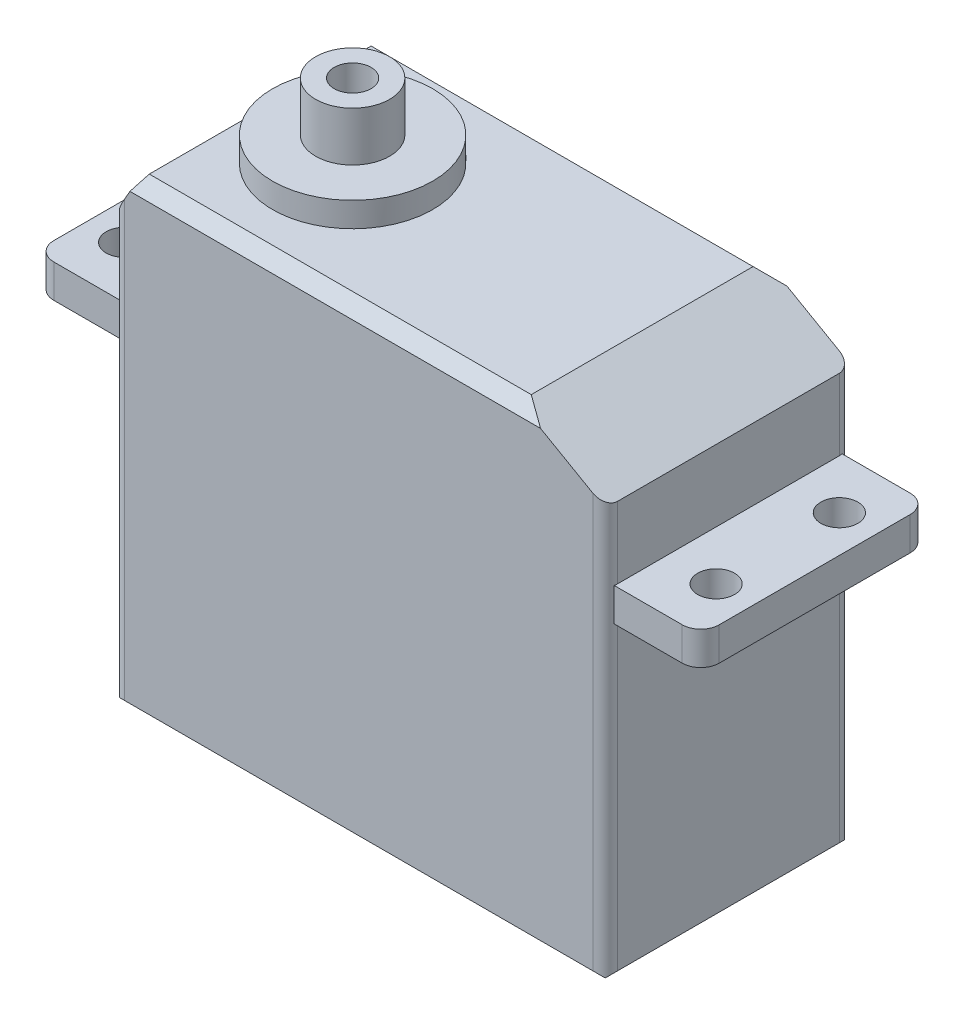
SolidWorks part; units mm, degrees
ref_plane "前视基准面" through (0, 0, 0) normal (0, 0, 1) x (1, 0, 0)
ref_plane "上视基准面" through (0, 0, 0) normal (0, 1, 0) x (1, 0, 0)
ref_plane "右视基准面" through (0, 0, 0) normal (1, 0, 0) x (0, 0, -1)
sketch "草图1" plane through (0, 0, 0) normal (0, 0, 1) x (1, 0, 0)
  line L1 (0, 0) -> (40, 0)
  line L2 (0, 0) -> (0, 39)
  line L3 (0, 39) -> (40, 39)
  line L4 (40, 0) -> (40, 39)
  dimension "D1" = 40
  dimension "D2" = 39
extrude "凸台-拉伸1" add sketch "草图1" along normal blind 20
sketch "草图2" plane through (0, 0, 0) normal (-1, 0, 0) x (0, 0, 1)
  line L0 (20, 0) -> (0, 0) construction
  line L1 (0.75, 29.2) -> (19.25, 29.2)
  line L2 (0.75, 29.2) -> (0.75, 26.5)
  line L3 (0.75, 26.5) -> (19.25, 26.5)
  line L4 (19.25, 29.2) -> (19.25, 26.5)
  line L5 (20, 39) -> (0, 39) construction
  point P8 (10, 39)
  point P9 (10, 29.2)
  dimension "D1" = 18.5
  dimension "D2" = 26.5
  dimension "D3" = 2.7
extrude "凸台-拉伸2" add sketch "草图2" along normal blind 7
sketch "草图3" plane through (40, 0, 0) normal (1, 0, 0) x (0, 0, -1)
  line L4 (-0.75, 26.5) -> (-0.75, 29.2)
  line L5 (-19.25, 26.5) -> (-0.75, 26.5)
  line L6 (-19.25, 29.2) -> (-19.25, 26.5)
  line L7 (-0.75, 29.2) -> (-19.25, 29.2)
  line L8 (-0.75, 26.5) -> (-0.75, 29.2)
  line L9 (-19.25, 26.5) -> (-0.75, 26.5)
  line L10 (-19.25, 29.2) -> (-19.25, 26.5)
  line L11 (-0.75, 29.2) -> (-19.25, 29.2)
  dimension "D1" = 0
extrude "凸台-拉伸3" add sketch "草图3" along normal blind 7
sketch "草图4" plane through (0, 29.2, 0) normal (0, 1, 0) x (1, 0, 0)
  line L0 (-4, -15) -> (-4, -5) construction
  line L1 (-4, -5) -> (44, -5) construction
  line L2 (40, 0) -> (0, 0) construction
  line L3 (-7, -19.25) -> (-7, -0.75) construction
  circle A0 centre (-4, -5) radius 1.5
  circle A1 centre (44, -5) radius 1.5
  circle A2 centre (-4, -15) radius 1.5
  circle A3 centre (44, -15) radius 1.5
  point P10 (20, 0)
  point P11 (20, -5)
  point P14 (-7, -10)
  point P15 (-4, -10)
  dimension "D3" = 3
  dimension "D4" = 3
  dimension "D5" = 3
  dimension "D6" = 3
  dimension "D1" = 48
  dimension "D2" = 10
extrude "切除-拉伸1" cut sketch "草图4" against normal blind 7
chamfer "倒角1" distance 2 angle 45 4 edges at (0, 0, 10) (20, 0, 20) (40, 0, 10) (20, 0, 0)
chamfer "倒角2" distance 2 distance2 3.5 1 edges at (0, 39, 10) first distance on face at (20, 39, 10)
chamfer "倒角3" distance 4 distance2 7 1 edges at (40, 39, 10) first distance on face at (40, 20.5, 10)
chamfer "倒角4" distance 1 angle 45 2 edges at (17.5, 39, 0) (17.5, 39, 20)
sketch "草图5" plane through (0, 39, 0) normal (0, 1, 0) x (1, 0, 0)
  line L0 (0, -19.25) -> (0, -0.75) construction
  line L1 (2, -1) -> (2, -19) construction
  circle A0 centre (9.5, -10) radius 6.5
  point P6 (2, -10)
  dimension "D2" = 13
  dimension "D1" = 9.5
extrude "凸台-拉伸4" add sketch "草图5" along normal blind 2
sketch "草图6" plane through (0, 41, 0) normal (0, 1, 0) x (1, 0, 0)
  circle A0 centre (9.5, -10) radius 3
  circle A1 centre (9.5, -10) radius 1.5
  dimension "D1" = 6
  dimension "D2" = 3
extrude "凸台-拉伸5" add sketch "草图6" along normal blind 4
fillet "圆角1" radius 1.5 4 edges at (47, 27.85, 0.75) (47, 27.85, 19.25) (-7, 27.85, 0.75) (-7, 27.85, 19.25)
fillet "圆角2" radius 1 4 edges at (0, 18.75, 20) (0, 18.75, 0) (40, 18.5, 0) (40, 18.5, 20)
